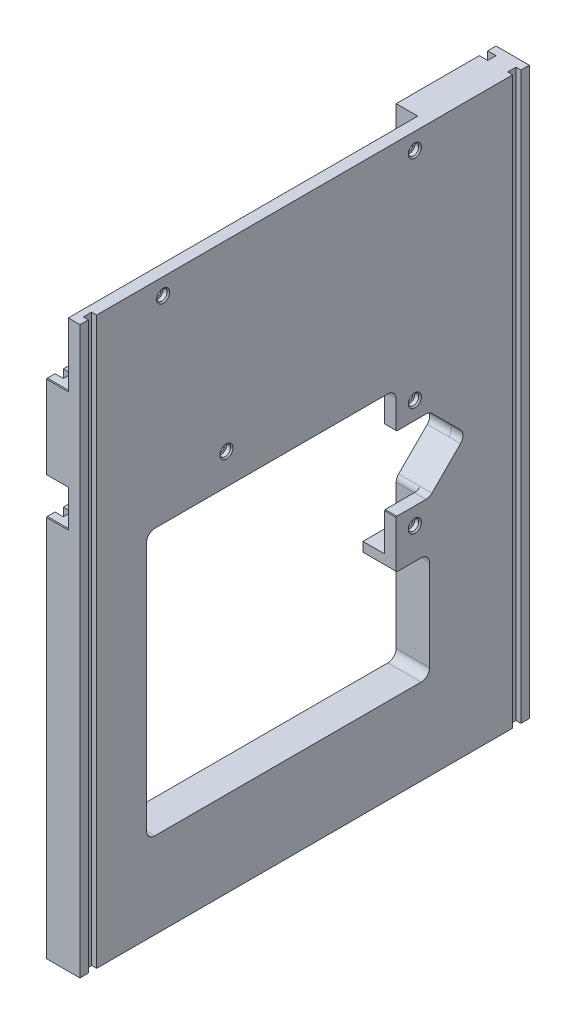
SolidWorks part; units mm, degrees
ref_plane "Front Plane" through (0, 0, 0) normal (0, 0, 1) x (1, 0, 0)
ref_plane "Top Plane" through (0, 0, 0) normal (0, 1, 0) x (1, 0, 0)
ref_plane "Right Plane" through (0, 0, 0) normal (1, 0, 0) x (0, 0, -1)
sketch "Sketch2" plane through (0, 0, 0) normal (1, 0, 0) x (0, 0, -1)
  line L1 (-215.489, 137.2751) -> (127.411, 137.2751)
  line L2 (-215.489, 137.2751) -> (-215.489, -294.5249)
  line L3 (-215.489, -294.5249) -> (127.411, -294.5249)
  line L4 (127.411, 137.2751) -> (127.411, -294.5249)
  dimension "D1" = 342.9
  dimension "D2" = 431.8
extrude "Base" add sketch "Sketch2" along normal blind 25.4
sketch "Sketch3" plane through (0, 0, 0) normal (1, 0, 0) x (0, 0, -1)
  line L0 (-44.039, -294.5249) -> (-44.039, 137.2751) construction
  line L1 (-215.489, -294.5249) -> (127.411, -294.5249) construction
  line L2 (-164.689, -25.9199) -> (-164.689, -229.1199)
  line L3 (-164.689, -229.1199) -> (51.211, -229.1199)
  line L4 (51.211, -146.9509) -> (51.211, -229.1199)
  line L5 (127.411, 137.2751) -> (-215.489, 137.2751) construction
  line L7 (-215.489, 137.2751) -> (-215.489, -294.5249) construction
  line L9 (51.211, -146.9509) -> (25.811, -146.9509)
  line L13 (-164.689, -25.9199) -> (25.811, -25.9199)
  line L14 (25.811, -146.9509) -> (25.811, -25.9199)
  dimension "D1" = 25.4
  dimension "D2" = 163.195
  dimension "D3" = 50.8
  dimension "D4" = 121.031
  dimension "D5" = 190.5
  dimension "D6" = 203.2
extrude "Cut-Extrude3" cut sketch "Sketch3" along normal up to next
sketch "Sketch4" plane through (0, 0, 0) normal (1, 0, 0) x (0, 0, -1)
  line L0 (-215.489, 137.2751) -> (-215.489, -294.5249) construction
  line L1 (19.461, -18.2999) -> (-158.339, -18.2999)
  line L2 (51.211, -15.1249) -> (51.211, 137.2751)
  line L3 (51.211, 137.2751) -> (-202.789, 137.2751)
  line L4 (-164.689, -12.5837) -> (-164.689, -2.4249)
  line L5 (51.211, -146.9509) -> (25.811, -146.9509) construction
  line L6 (25.811, -25.9199) -> (-164.689, -25.9199) construction
  line L7 (-164.689, 24.8801) -> (-215.489, 24.8801)
  line L8 (51.211, -15.1249) -> (51.211, -53.8599)
  line L9 (44.861, -139.3309) -> (25.811, -139.3309)
  line L10 (25.811, -25.9199) -> (25.811, -139.3309)
  line L11 (25.811, -25.9199) -> (-164.689, -25.9199) construction
  line L12 (25.811, -25.9199) -> (19.461, -25.9199)
  line L13 (19.461, -18.2999) -> (19.461, -25.9199)
  line L14 (51.211, -136.1559) -> (51.211, -146.9509)
  line L15 (51.211, -146.9509) -> (44.861, -146.9509)
  line L16 (44.861, -139.3309) -> (44.861, -146.9509)
  line L17 (-44.039, 137.2751) -> (-44.039, -294.5249) construction
  line L18 (-164.689, -12.5837) -> (-164.689, -25.9199)
  line L19 (-164.689, -25.9199) -> (-158.339, -25.9199)
  line L20 (-158.339, -18.2999) -> (-158.339, -25.9199)
  line L22 (-215.489, -294.5249) -> (127.411, -294.5249) construction
  line L23 (51.211, -110.2479) -> (79.405, -82.0539)
  line L24 (-164.689, -2.4249) -> (-215.489, -2.4249)
  line L25 (-215.489, 24.8801) -> (-215.489, -2.4249)
  line L26 (-164.689, 24.8801) -> (-164.689, 89.0151)
  line L27 (-202.789, 137.2751) -> (-215.489, 137.2751)
  line L28 (79.405, -82.0539) -> (51.211, -53.8599)
  line L29 (-164.689, 89.0151) -> (-215.489, 89.0151)
  line L30 (-215.489, 137.2751) -> (-215.489, 90.2851)
  line L31 (-215.489, 90.2851) -> (-215.489, 89.0151)
  line L32 (51.211, -110.2479) -> (51.211, -136.1559)
  dimension "D2" = 7.62
  dimension "D3" = 15.875
  dimension "D4" = 276.606
  dimension "D5" = 25.4
  dimension "D6" = 6.35
  dimension "D7" = 6.35
  dimension "D8" = 7.62
  dimension "D9" = 6.35
  dimension "D10" = 48.26
  dimension "D11" = 43.18
  dimension "D12" = 215.9
  dimension "D13" = 266.7
  dimension "D15" = 45
  dimension "D16" = 29.083
  dimension "D17" = 56.388
extrude "NC pocket" cut sketch "Sketch4" along normal blind 16.51
fillet "Fillet9" radius 6.35 2 edges at (8.255, -110.2479, -51.211) (8.255, -53.8599, -51.211)
fillet "Fillet6" radius 6.35 1 edges at (8.255, -82.0539, -79.405)
hole_wizard "CBORE for M4 SHCS1" positions "Sketch8" profile "Sketch10" counterbore size "M4" standard "ANSI Metric" end condition up to next
sketch "Sketch8" plane through (25.4, 0, 0) normal (1, 0, 0) x (0, 0, -1)
  line L1 (127.411, 137.2751) -> (-215.489, 137.2751) construction
  line L4 (-164.689, -2.4249) -> (-164.689, -229.1199) construction
  line L5 (51.211, -229.1199) -> (51.211, -112.8782) construction
  line L6 (-158.339, -18.2999) -> (19.461, -18.2999) construction
  point P0 (-151.989, 124.5751)
  point P5 (40.035, 124.5751)
  point P7 (40.035, -123.4559)
  point P9 (40.035, -40.5249)
  point P11 (-103.729, -2.4249)
  dimension "D2" = 12.7
  dimension "D3" = 12.7
  dimension "D4" = 11.176
  dimension "D5" = 60.96
  dimension "D6" = 15.875
  dimension "D7" = 11.176
  dimension "D8" = 165.1
  dimension "D9" = 11.176
  dimension "D10" = 82.931
  dimension "D11" = 12.7
sketch "Sketch10" plane through (25.4, 124.5751, 151.989) normal (0, 1, 0) x (0, 0, -1)
  line L0 (0, 0) -> (0, 8.89)
  line L1 (0, 8.89) -> (2.15, 8.89)
  line L3 (2.15, 8.89) -> (2.15, 4)
  line L4 (4, 4) -> (2.15, 4)
  line L5 (4, 4) -> (4, 1)
  line L6 (4, 1) -> (5, 0)
  line L7 (5, 0) -> (0, 0)
  line L8 (-4, 1) -> (-5, 0) construction
  line L11 (0, -6.35) -> (0, 107.95) construction
  dimension "Thru Hole Dia." = 4.3
  dimension "Thru Hole Depth" = 8.89
  dimension "C'Bore Dia." = 8
  dimension "C'Bore Depth" = 4
  dimension "Near C'Sink Dia." = 10
  dimension "Near C'Sink Angle" = 90
sketch "Sketch18" plane through (16.51, 0, 0) normal (-1, 0, 0) x (0, 0, 1)
  circle A0 centre (-40.035, 124.5751) radius 7.1755
  circle A1 centre (151.989, 124.5751) radius 7.1755
  circle A2 centre (103.729, -2.4249) radius 7.1755
  circle A3 centre (-40.035, -40.5249) radius 7.1755
  circle A4 centre (-40.035, -123.4559) radius 7.1755
  dimension "D1" = 14.351
  dimension "D2" = 14.351
  dimension "D3" = 14.351
  dimension "D4" = 14.351
  dimension "D5" = 14.351
extrude "Cut-Extrude4" cut sketch "Sketch18" against normal blind 1.016
hole_wizard "3/8-16 Tapped Hole1" positions "3DSketch1" profile "Sketch14" tap size "3/8-16" standard "ANSI Inch"
sketch3d "3DSketch1"
  line L0 (0, -294.5249, 215.489) -> (0, -294.5249, -127.411) construction
  line L1 (25.4, -294.5249, 215.489) -> (0, -294.5249, 215.489) construction
  point P0 (12.7, -294.5249, -70.261)
  point P2 (12.7, -294.5249, 44.039)
  point P4 (12.7, -294.5249, 158.339)
  dimension "D1" = 12.7
  dimension "D2" = 12.7
  dimension "D3" = 12.7
  dimension "D4" = 114.3
  dimension "D6" = 114.3
  dimension "D5" = 171.45
sketch "Sketch14" plane through (12.7, -294.5249, -70.261) normal (1, 0, 0) x (0, 0, -1)
  line L0 (0, 0) -> (0, 30.3247)
  line L1 (0, 30.3247) -> (3.9687, 27.94)
  line L2 (3.9687, 27.94) -> (3.9687, 0)
  line L5 (3.9687, 0) -> (0, 0)
  line L10 (0, 30.3247) -> (-3.9688, 27.94) construction
  line L11 (0, -6.35) -> (0, 107.95) construction
  dimension "Tap Drill Dia." = 7.9375
  dimension "Tap Drill Depth" = 27.94
  dimension "Drill Angle" = 118
cosmetic thread "Hole Thread1" parameters "D1"=25.4, "D2"=9.525
cosmetic thread "Hole Thread2" parameters "D1"=25.4, "D2"=9.525
cosmetic thread "Hole Thread3" parameters "D1"=25.4, "D2"=9.525
hole_wizard "3/8-16 Tapped Hole2" positions "Sketch15" profile "Sketch17" tap size "3/8-16" standard "ANSI Inch"
sketch "Sketch15" plane through (0, 0, 0) normal (-1, 0, 0) x (0, 0, 1)
  line L0 (215.489, -2.4249) -> (215.489, -294.5249) construction
  line L1 (-127.411, -294.5249) -> (-127.411, 137.2751) construction
  line L2 (215.489, -294.5249) -> (-127.411, -294.5249) construction
  point P0 (190.089, -220.8649)
  point P2 (190.089, -162.4449)
  point P4 (-102.011, -220.8649)
  point P6 (-102.011, -162.4449)
  dimension "D1" = 25.4
  dimension "D2" = 25.4
  dimension "D3" = 25.4
  dimension "D4" = 25.4
  dimension "D5" = 73.66
  dimension "D6" = 58.42
  dimension "D7" = 58.42
  dimension "D8" = 73.66
cosmetic thread "Hole Thread4" parameters "D1"=17.78, "D2"=9.525
cosmetic thread "Hole Thread5" parameters "D1"=17.78, "D2"=9.525
cosmetic thread "Hole Thread6" parameters "D1"=17.78, "D2"=9.525
cosmetic thread "Hole Thread7" parameters "D1"=17.78, "D2"=9.525
sketch "Sketch17" plane through (0, -220.8649, 190.089) normal (0, 1, 0) x (0, 0, 1)
  line L0 (0, 0) -> (0, 22.7047)
  line L1 (0, 22.7047) -> (3.9687, 20.32)
  line L2 (3.9687, 20.32) -> (3.9687, 0)
  line L5 (3.9687, 0) -> (0, 0)
  line L10 (0, 22.7047) -> (-3.9688, 20.32) construction
  line L11 (0, -6.35) -> (0, 107.95) construction
  dimension "Tap Drill Dia." = 7.9375
  dimension "Tap Drill Depth" = 20.32
  dimension "Drill Angle" = 118
sketch "Sketch20" plane through (16.51, 0, 0) normal (-1, 0, 0) x (0, 0, 1)
  line L0 (-51.211, -53.8599) -> (-25.811, -53.8599)
  line L2 (-51.211, -53.8599) -> (-79.405, -82.0539)
  line L3 (-79.405, -82.0539) -> (-51.211, -110.2479)
  line L4 (-25.811, -25.9199) -> (-25.811, -139.3309) construction
  line L6 (-25.811, -53.8599) -> (-25.811, -110.2479)
  line L7 (-25.811, -110.2479) -> (-51.211, -110.2479)
  line L8 (-51.211, -45.3946) -> (-51.211, -54.9122) construction
  line L9 (-51.211, -51.2297) -> (-51.211, 137.2751) construction
  line L10 (-51.211, -116.8371) -> (-51.211, -107.9924) construction
  line L11 (-51.211, -146.9509) -> (-51.211, -112.8782) construction
  line L12 (-74.9149, -77.5638) -> (-53.0709, -55.7198) construction
  line L13 (-53.0709, -108.388) -> (-74.9149, -86.544) construction
extrude "Cut-Extrude5" cut sketch "Sketch20" against normal up to next
fillet "Fillet1" radius 6.35 5 edges at (20.955, -25.9199, 164.689) (12.7, -229.1199, 164.689) (12.7, -229.1199, -51.211) (20.955, -146.9509, -51.211) (20.955, -25.9199, -25.811)
fillet "Fillet2" radius 6.35 3 edges at (20.955, -82.0539, -79.405) (20.955, -110.2479, -51.211) (20.955, -53.8599, -51.211)
chamfer "Chamfer1" distance 0.508 angle 45 9 edges at (8.255, -2.4249, 215.489) (8.255, -2.4249, 164.689) (8.255, 24.8801, 215.489) (8.255, 24.8801, 164.689) (8.255, 89.0151, 215.489) (8.255, 89.0151, 164.689) (12.7, -146.9509, -25.811) (20.955, -110.2479, -25.811) (20.955, -53.8599, -25.811)
sketch "Sketch21" plane through (0, 0, 0) normal (-1, 0, 0) x (0, 0, 1)
  line L0 (215.489, -294.5249) -> (-127.411, -294.5249) construction
  line L1 (209.139, -294.5249) -> (202.789, -294.5249)
  line L2 (209.139, -294.5249) -> (209.139, 137.2751)
  line L3 (209.139, 137.2751) -> (202.789, 137.2751)
  line L4 (202.789, -294.5249) -> (202.789, 137.2751)
  line L5 (-127.411, 137.2751) -> (-51.211, 137.2751) construction
  line L6 (215.489, -2.9329) -> (215.489, -294.5249) construction
  line L7 (-127.411, -294.5249) -> (-127.411, 137.2751) construction
  line L8 (-114.711, -294.5249) -> (-121.061, -294.5249)
  line L9 (-114.711, -294.5249) -> (-114.711, 137.2751)
  line L10 (-114.711, 137.2751) -> (-121.061, 137.2751)
  line L11 (-121.061, -294.5249) -> (-121.061, 137.2751)
  dimension "D1" = 6.35
  dimension "D2" = 6.35
  dimension "D3" = 6.35
  dimension "D4" = 6.35
extrude "Cut-Extrude6" cut sketch "Sketch21" against normal blind 6.35
sketch "Sketch22" plane through (25.4, 0, 0) normal (1, 0, 0) x (0, 0, -1)
  line L0 (-215.489, -294.5249) -> (127.411, -294.5249) construction
  line L1 (-202.789, -294.5249) -> (-209.139, -294.5249)
  line L2 (-202.789, -294.5249) -> (-202.789, 137.2751)
  line L3 (-202.789, 137.2751) -> (-209.139, 137.2751)
  line L4 (-209.139, -294.5249) -> (-209.139, 137.2751)
  line L5 (127.411, 137.2751) -> (-215.489, 137.2751) construction
  line L6 (-215.489, 137.2751) -> (-215.489, -294.5249) construction
  line L7 (127.411, -294.5249) -> (127.411, 137.2751) construction
  line L8 (114.711, 137.2751) -> (121.061, 137.2751)
  line L9 (114.711, 137.2751) -> (114.711, -294.5249)
  line L10 (114.711, -294.5249) -> (121.061, -294.5249)
  line L11 (121.061, 137.2751) -> (121.061, -294.5249)
  dimension "D1" = 6.35
  dimension "D2" = 6.35
  dimension "D3" = 6.35
  dimension "D4" = 6.35
extrude "Cut-Extrude7" cut sketch "Sketch22" against normal blind 3.81
